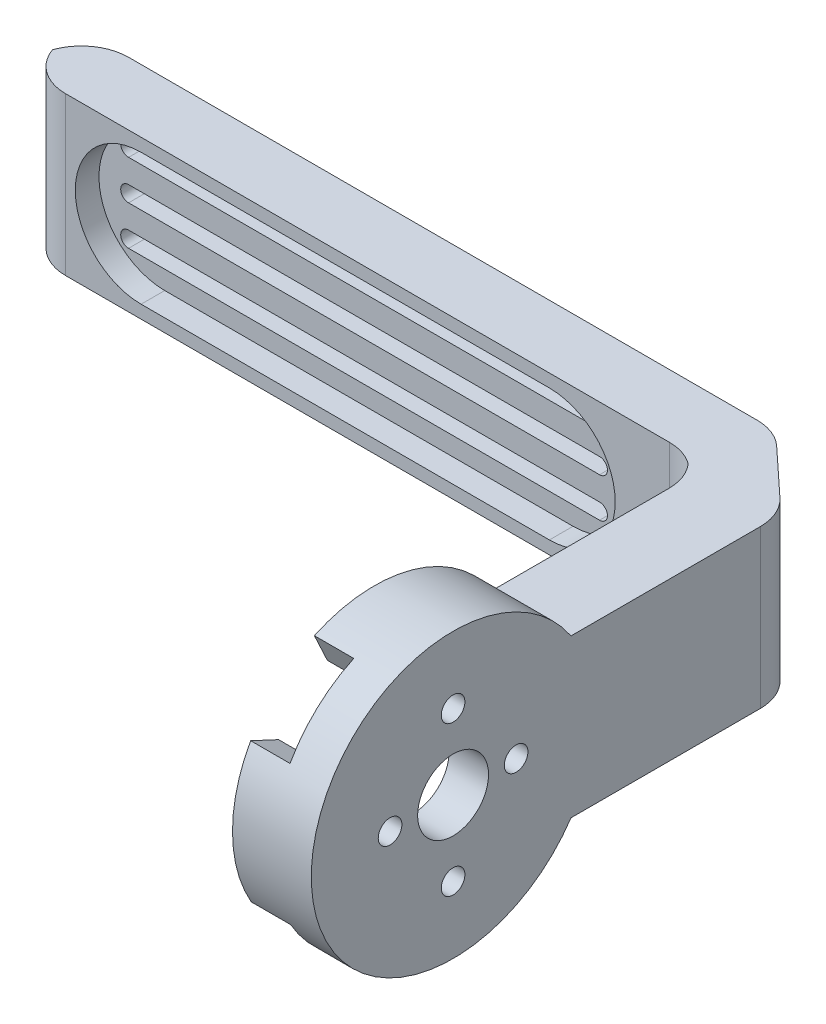
SolidWorks part; units mm, degrees
ref_plane "Front Plane" through (0, 0, 0) normal (0, 0, 1) x (1, 0, 0)
ref_plane "Top Plane" through (0, 0, 0) normal (0, 1, 0) x (1, 0, 0)
ref_plane "Right Plane" through (0, 0, 0) normal (1, 0, 0) x (0, 0, -1)
sketch "Sketch2" plane through (0, 0, 0) normal (0, 1, 0) x (1, 0, 0)
  line L0 (-85, 8) -> (-85, 0)
  line L1 (-85, 0) -> (0, 0)
  line L2 (0, 0) -> (2.6896, -2.5)
  line L3 (2.6896, -2.5) -> (2.6896, -42.5)
  line L4 (2.6896, -42.5) -> (12.6896, -42.5)
  line L5 (12.6896, -42.5) -> (12.6896, -0.8728)
  line L6 (12.6896, -0.8728) -> (3.1438, 8)
  line L7 (3.1438, 8) -> (-85, 8)
  dimension "D1" = 8
  dimension "D2" = 8
  dimension "D3" = 10
  dimension "D4" = 85
  dimension "D5" = 40
  dimension "D6" = 42.5
extrude "Boss-Extrude1" add sketch "Sketch2" along normal blind 10 and the other way blind 10
fillet "Fillet1" radius 6 4 edges at (2.6896, 0, 2.5) (0, 0, 0) (12.6896, 0, 0.8728) (3.1438, 0, -8)
sketch "Sketch7" plane through (12.6896, 0, 0) normal (1, 0, 0) x (0, 0, -1)
  line L5 (-42.5, -10) -> (-42.5, 10) construction
  circle A4 centre (-42.5, 0) radius 18
extrude "Boss-Extrude3" add sketch "Sketch7" against normal up to surface (10 mm away) up to face at (2.6896, 0, 23.8073)
fillet "Fillet4" radius 6 2 edges at (-85, 0, -8) (-85, 0, 0)
sketch "Sketch13" plane through (0, 0, -8) normal (0, 0, -1) x (-1, 0, 0)
  line L0 (79, 0) -> (74, 0) construction
  line L1 (79, -10) -> (79, 10) construction
  line L2 (74, 0) -> (14.214, 0) construction
  line L3 (74, -1) -> (14.214, -1)
  line L4 (74, 1) -> (14.214, 1)
  line L5 (74, 5) -> (14.214, 5) construction
  line L8 (74, 4) -> (14.214, 4)
  line L11 (14.214, 0) -> (74, 0) construction
  line L12 (-0.786, 0) -> (14.214, 0) construction
  line L13 (-0.786, 10) -> (-0.786, -10) construction
  line L14 (74, 6) -> (14.214, 6)
  line L15 (74, -5) -> (14.214, -5) construction
  line L16 (74, -6) -> (14.214, -6)
  line L17 (74, -4) -> (14.214, -4)
  arc A0 (74, -1) -> (74, 1) centre (74, 0) ccw
  arc A1 (14.214, 1) -> (14.214, -1) centre (14.214, 0) ccw
  arc A6 (74, 4) -> (74, 6) centre (74, 5) ccw
  arc A7 (14.214, 6) -> (14.214, 4) centre (14.214, 5) ccw
  arc A8 (74, -6) -> (74, -4) centre (74, -5) ccw
  arc A9 (14.214, -4) -> (14.214, -6) centre (14.214, -5) ccw
  point P5 (44.107, 0)
  point P13 (44.107, 5)
  point P19 (44.107, -5)
  dimension "D1" = 2
  dimension "D2" = 2
extrude "Cut-Extrude7" cut sketch "Sketch13" against normal up to surface (8 mm away) up to face at (-40.6789, 0, 0)
sketch "Sketch15" plane through (0, 0, -8) normal (0, 0, -1) x (-1, 0, 0)
  line L0 (74, 0) -> (14.214, 0) construction
  line L1 (74, -4.5) -> (14.214, -4.5)
  line L2 (74, 4.5) -> (14.214, 4.5)
  arc A0 (74, -4.5) -> (74, 4.5) centre (74, 0) ccw
  arc A1 (14.214, 4.5) -> (14.214, -4.5) centre (14.214, 0) ccw
  point P4 (44.107, 0)
extrude "Cut-Extrude8" cut sketch "Sketch15" against normal blind 1
sketch "Sketch16" plane through (2.6896, 0, 0) normal (-1, 0, 0) x (0, 0, 1)
  circle A0 centre (42.5, 0) radius 14.1
extrude "Cut-Extrude9" cut sketch "Sketch16" against normal blind 5
sketch "Sketch17" plane through (2.6896, 0, 0) normal (-1, 0, 0) x (0, 0, 1)
  line L0 (42.5, 0) -> (60.5, 0) construction
  line L1 (50.9458, 5.4297) -> (58.1962, 8.8107) construction
  line L2 (50.119, -5.2165) -> (58.119, -8.947) construction
  line L3 (42.5, 0) -> (50.1071, -16.3135) construction
  line L4 (42.5, 0) -> (50.1071, 16.3135) construction
  line L5 (42.5, 0) -> (50.1071, -16.3135)
  line L6 (50.1071, 16.3135) -> (42.5, 0)
  line L7 (58.119, -8.947) -> (50.119, -5.2165)
  line L8 (58.1962, 8.8107) -> (50.9458, 5.4297)
  line L9 (50.119, -5.2165) -> (50.9458, 5.4297)
  arc A0 (27.5334, -10) -> (27.5334, 10) centre (42.5, 0) ccw construction
  arc A1 (50.1071, -16.3135) -> (58.119, -8.947) centre (42.5, 0) ccw
  arc A2 (58.1962, 8.8107) -> (50.1071, 16.3135) centre (42.5, 0) ccw
  point P13 (42.5, 0)
  point P17 (42.5, 0)
  dimension "D1" = 25
  dimension "D2" = 25
  dimension "D3" = 40
  dimension "D4" = 40
  dimension "D5" = 8
  dimension "D6" = 8
  dimension "D7" = 8
extrude "Cut-Extrude10" cut sketch "Sketch17" against normal up to surface (5 mm away) up to face at (7.6896, 0, 56.6)
sketch "Sketch18" plane through (7.6896, 0, 0) normal (-1, 0, 0) x (0, 0, 1)
  line L0 (50.5, 0) -> (34.5, 0) construction
  line L1 (42.5, -9.5) -> (42.5, 9.5) construction
  circle A0 centre (34.5, 0) radius 1.5
  circle A1 centre (42.5, -9.5) radius 1.5
  circle A2 centre (50.5, 0) radius 1.5
  circle A3 centre (42.5, 9.5) radius 1.5
  circle A4 centre (42.5, 0) radius 4.5
  arc A5 (58.119, -8.947) -> (58.1962, 8.8107) centre (42.5, 0) ccw construction
  point P6 (42.5, 0)
  point P10 (42.5, 0)
  dimension "D1" = 8
  dimension "D2" = 19
  dimension "D3" = 16
extrude "Cut-Extrude11" cut sketch "Sketch18" against normal up to surface (5 mm away) up to face at (12.6896, 0, 23.7521)
sketch "Sketch22" plane through (0, 0, 0) normal (0, 0, 1) x (1, 0, 0)
  line L0 (-69.411, 0) -> (-17.582, 0) construction
  line L3 (-69.411, 8.3513) -> (-17.582, 8.3513)
  line L4 (-69.411, -8.3513) -> (-17.582, -8.3513)
  arc A2 (-69.411, 8.3513) -> (-69.411, -8.3513) centre (-69.411, 0) ccw
  arc A3 (-17.582, -8.3513) -> (-17.582, 8.3513) centre (-17.582, 0) ccw
  point P3 (-43.4965, 0)
  point P8 (-53.8927, 0)
  point P9 (-69.411, 0)
  point P11 (-17.582, 0)
extrude "Cut-Extrude12" cut sketch "Sketch22" against normal blind 3
